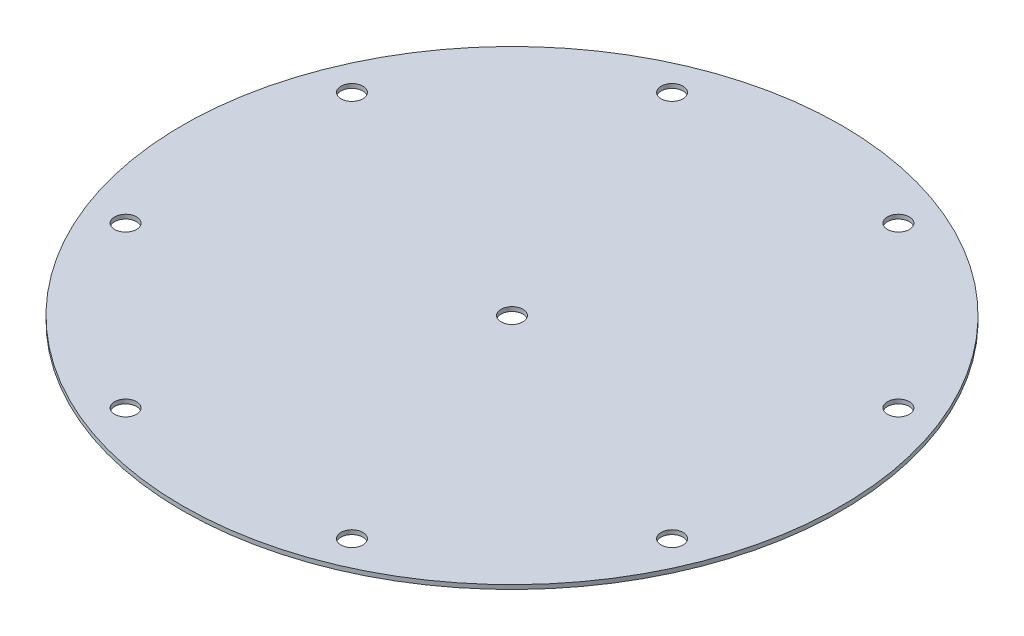
SolidWorks part; units mm, degrees
ref_plane "Front Plane" through (0, 0, 0) normal (0, 0, 1) x (1, 0, 0)
ref_plane "Top Plane" through (0, 0, 0) normal (0, 1, 0) x (1, 0, 0)
ref_plane "Right Plane" through (0, 0, 0) normal (1, 0, 0) x (0, 0, -1)
sketch "Sketch2" plane through (0, 0, 0) normal (1, 0, 0) x (0, 0, -1)
  line L0 (0, 0) -> (-77.9998, 0)
  line L1 (-77.9998, 0) -> (-77.9998, 1)
  line L2 (-77.9998, 1) -> (0, 1)
  line L5 (0, 1) -> (0, 0)
  dimension "D1" = 77.9998
  dimension "D2" = 1
ref_axis "Axis1" through (0, -0.05, 0) along (0, 1, 0)
revolve "Revolve1" add sketch "Sketch2" angle 360 about axis through (0, -0.05, 0) along (0, 1, 0)
hole_wizard "#6 (0.204) Diameter Hole1" positions "Sketch6" profile "Sketch7" hole size "#6" standard "ANSI Inch" end condition through all
sketch "Sketch6" plane through (0, 1, 0) normal (0, 1, 0) x (1, 0, 0)
  line L0 (0, 0) -> (-53.438, 129.0108) construction
  line L2 (0, 0) -> (0, 109.0908) construction
  point P0 (-26.7878, 64.6716)
  dimension "D1" = 22.5
  dimension "D2" = 70
sketch "Sketch7" plane through (-26.7878, 1, -64.6716) normal (1, 0, 0) x (0, 0, 1)
  line L0 (0, 0) -> (0, 1)
  line L1 (0, 1) -> (2.5908, 1)
  line L2 (2.5908, 1) -> (2.5908, 0)
  line L5 (2.5908, 0) -> (0, 0)
  line L11 (0, -6.35) -> (0, 107.95) construction
  dimension "Thru Hole Dia." = 5.1816
  dimension "Thru Hole Depth" = 1
pattern_circular "CirPattern3" count 8 over 360 about axis through (0, -0.05, 0) along (0, 1, 0) of "#6 (0.204) Diameter Hole1"
hole_wizard "#6 (0.204) Diameter Hole2" positions "Sketch8" profile "Sketch9" hole size "#6" standard "ANSI Inch" end condition through all
sketch "Sketch8" plane through (0, 1, 0) normal (0, 1, 0) x (1, 0, 0)
  line L0 (0, 0) -> (106.3094, -1.7118) construction
  point P7 (0, 0)
sketch "Sketch9" plane through (0, 1, 0) normal (1, 0, 0) x (0, 0, 1)
  line L0 (0, 0) -> (0, 1)
  line L1 (0, 1) -> (2.5908, 1)
  line L2 (2.5908, 1) -> (2.5908, 0)
  line L5 (2.5908, 0) -> (0, 0)
  line L11 (0, -6.35) -> (0, 107.95) construction
  dimension "Thru Hole Dia." = 5.1816
  dimension "Thru Hole Depth" = 1
equation "\"TubeDiameter\" = 6.6929in"
equation "\"D1@Sketch2\"=\"TubeDiameter\"/2-7mm"
